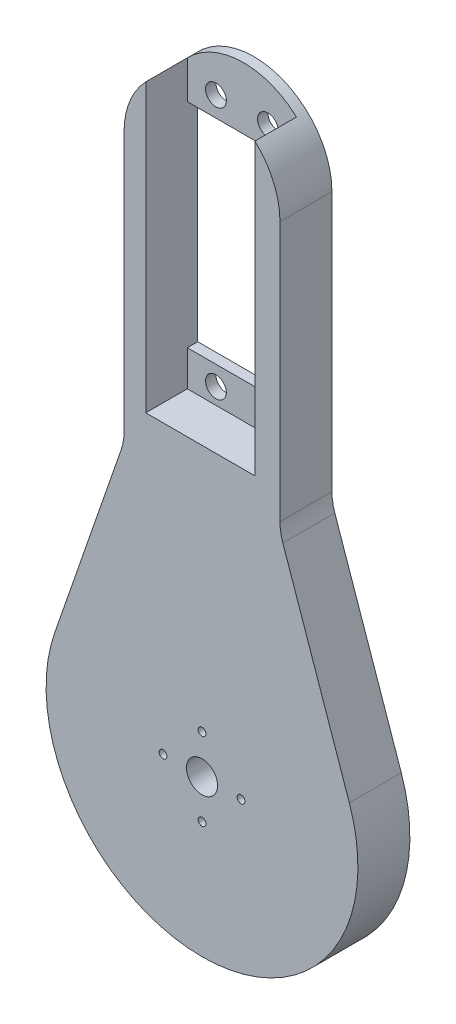
SolidWorks part; units mm, degrees
ref_plane "Plan de face" through (0, 0, 0) normal (0, 0, 1) x (1, 0, 0)
ref_plane "Plan de dessus" through (0, 0, 0) normal (0, 1, 0) x (1, 0, 0)
ref_plane "Plan de droite" through (0, 0, 0) normal (1, 0, 0) x (0, 0, -1)
sketch "Esquisse1" plane through (0, 0, 0) normal (0, 0, 1) x (1, 0, 0)
  line L0 (0, 0) -> (0, 100) construction
  line L1 (-15, 100) -> (-15, 50)
  line L2 (15, 100) -> (15, 50)
  line L3 (-15.5518, 46.7241) -> (-28.3446, 9.8277)
  line L4 (15.5518, 46.7241) -> (28.3446, 9.8277)
  line L5 (-0.3232, 109.9293) -> (-0.3232, 62.0793) construction
  line L6 (-10.8232, 109.9293) -> (10.1768, 109.9293)
  line L7 (-10.8232, 62.0793) -> (10.1768, 62.0793)
  line L8 (-10.8232, 92.7793) -> (10.1768, 92.7793) construction
  line L9 (-10.8232, 103.0793) -> (10.1768, 103.0793)
  line L10 (-5.3232, 58.3286) -> (-5.3232, 106.9586) construction
  line L11 (-10.8232, 62.0793) -> (10.1768, 62.0793)
  line L12 (-10.8232, 62.0793) -> (-10.8232, 55.2293)
  line L13 (-10.8232, 55.2293) -> (10.1768, 55.2293)
  line L14 (10.1768, 62.0793) -> (10.1768, 55.2293)
  line L15 (-10.8232, 106.9586) -> (10.1768, 106.9586) construction
  line L16 (-5.3232, 58.3286) -> (-10.8232, 58.3286) construction
  line L17 (-5.3232, 58.3286) -> (10.1768, 58.3286) construction
  line L18 (-10.8232, 106.9586) -> (10.1768, 58.3286) construction
  line L19 (-10.8232, 58.3286) -> (10.1768, 106.9586) construction
  line L20 (-0.3232, 82.6436) -> (-10.8232, 82.6436) construction
  line L21 (-0.3232, 62.0793) -> (-0.3232, 55.2293) construction
  line L22 (-10.8232, 103.0793) -> (-10.8232, 62.0793)
  line L23 (-10.8232, 109.9293) -> (-10.8232, 103.0793)
  line L24 (10.1768, 103.0793) -> (10.1768, 62.0793)
  line L25 (10.1768, 109.9293) -> (10.1768, 103.0793)
  line L26 (-10.8232, 109.9293) -> (-10.8232, 110.3855)
  line L27 (10.1768, 109.9293) -> (10.1768, 111.0197)
  arc A0 (-28.3446, 9.8277) -> (28.3446, 9.8277) centre (0, 0) ccw
  circle A2 centre (0, -7.5) radius 0.75
  arc A7 (15, 50) -> (15.5518, 46.7241) centre (25, 50) ccw
  arc A8 (-15, 50) -> (-15.5518, 46.7241) centre (-25, 50) cw
  arc A9 (15, 100) -> (-15, 100) centre (0, 100) ccw
  circle A10 centre (-5.3232, 106.9586) radius 2
  circle A11 centre (-5.3232, 58.3286) radius 2
  circle A12 centre (4.6768, 58.3286) radius 2
  circle A13 centre (4.6768, 106.9586) radius 2
  circle A17 centre (0, 0) radius 7.5
  circle A18 centre (-7.5, 0) radius 0.75
  circle A19 centre (0, 7.5) radius 0.75
  circle A20 centre (7.5, 0) radius 0.75
  circle A21 centre (0, 0) radius 3
  point P26 (15, 48.3156)
  point P29 (-15, 48.3156)
  point P59 (0, 0)
  point P60 (0, 0)
  dimension "D1" = 60
  dimension "D2" = 1.5
  dimension "D3" = 15
  dimension "D6" = 10
  dimension "D7" = 50
  dimension "D12" = 4
  dimension "D13" = 4
  dimension "D18" = 6
  dimension "D4" = 100
  dimension "D5" = 15
  dimension "D8" = 17.15
  dimension "D9" = 6.85
  dimension "D10" = 41
  dimension "D11" = 6.85
  dimension "D14" = 48.63
  dimension "D15" = 21
  dimension "D16" = 5
  dimension "D17" = 4
extrude "Boss.-Extru.1" add sketch "Esquisse1" along normal blind 2 contours L2 A9 L27 L25 L24 L14 L13 L12 L22 L23 L26 L1 A8 L3 A0 L4 A7 A2 | L27 A9 L26 L6 | L25 L6 L23 L9 A10 A13 | L14 L7 L12 L13 A11 A12 | A2 region at (0.0906, 18.9962, 0) region at (-0.0673, 112.0055, 0) region at (-0.3232, 106.4081, 0) region at (-0.3232, 58.7233, 0) region at (0, -6.5389, 0)
extrude "Boss.-Extru.2" add sketch "Esquisse1<3>" along normal blind 8 from surface contours L2 A9 L27 L25 L24 L14 L13 L12 L22 L23 L26 L1 A8 L3 A0 L4 A7 A2 | A2 region at (0.0906, 18.9962, 0) region at (0, -6.5389, 0) starting at face at (8.25, 0, 2)
sketch "Esquisse1<3>" plane through (0, 0, 0) normal (0, 0, 1) x (1, 0, 0) same geometry as "Esquisse1"
